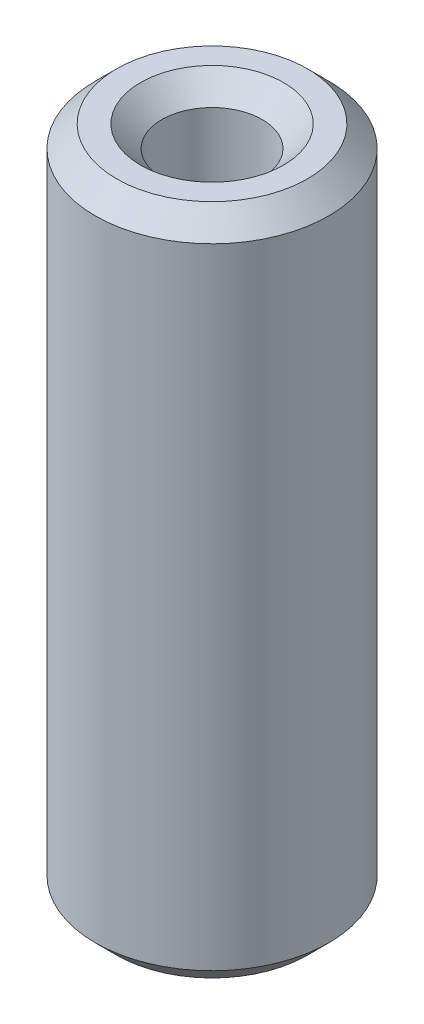
SolidWorks part; units mm, degrees
ref_plane "Front Plane" through (0, 0, 0) normal (0, 0, 1) x (1, 0, 0)
ref_plane "Top Plane" through (0, 0, 0) normal (0, 1, 0) x (1, 0, 0)
ref_plane "Right Plane" through (0, 0, 0) normal (1, 0, 0) x (0, 0, -1)
sketch "Sketch1" plane through (0, 0, 0) normal (0, 1, 0) x (1, 0, 0)
  circle A0 centre (0, 0) radius 17.5
  dimension "SLEEVE_OD" = 35
extrude "Boss-Extrude1" add sketch "Sketch1" along normal blind 100.7657
sketch "Sketch2" plane through (0, 0, 0) normal (0, 1, 0) x (1, 0, 0)
  circle A0 centre (0, 0) radius 7.523
  dimension "BORE_D" = 15.046
extrude "Cut-Extrude1" cut sketch "Sketch2" along normal through all
chamfer "Chamfer1" distance 3.2018 angle 45 4 edges at (0, 100.7657, 7.523) (0, 0, 7.523) (0, 0, 17.5) (0, 100.7657, 17.5)
